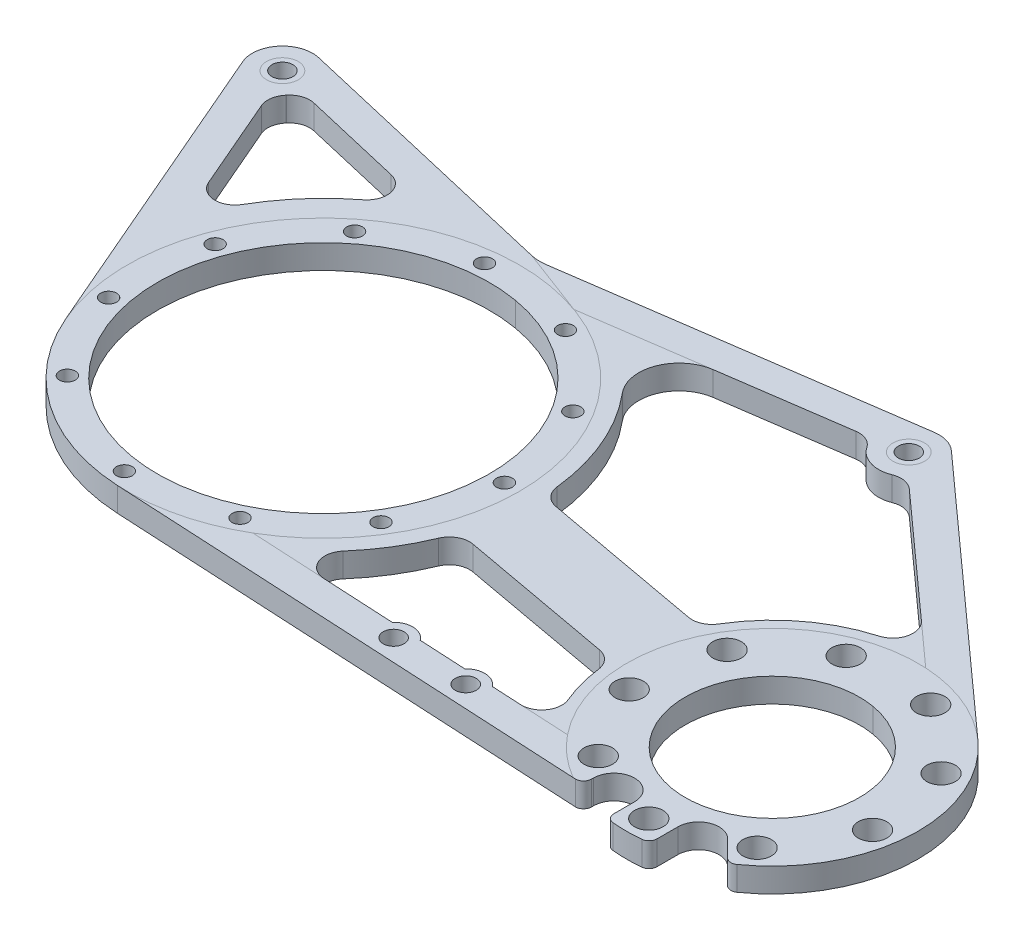
SolidWorks part; units mm, degrees
material "6061-T6 (SS)"
ref_plane "X-Y Datum" through (0, 0, 0) normal (0, 0, 1) x (1, 0, 0)
ref_plane "X-Z Datum" through (0, 0, 0) normal (0, 1, 0) x (1, 0, 0)
ref_plane "Y-Z Datum" through (0, 0, 0) normal (1, 0, 0) x (0, 0, -1)
sketch "Sketch2" plane through (0, 31.3819, 0) normal (0, 1, 0) x (1, 0, 0)
  line L0 (-693.7583, -176.702) -> (-693.7583, -183.2747) construction
  line L1 (-680.0808, -183.2747) -> (-680.0808, -176.702) construction
  line L2 (-668.9846, -172.1058) -> (-663.7197, -177.3707) construction
  line L3 (-693.7583, -176.702) -> (-693.7583, -183.2747)
  line L4 (-680.0808, -183.2747) -> (-680.0808, -176.702)
  line L5 (-668.9846, -172.1058) -> (-663.7197, -177.3707)
  line L6 (-966.641, -0.354) -> (-738.041, -0.354)
  line L7 (-727.7656, -5.5904) -> (-649.7224, -113.0358)
  line L9 (-977.8288, -19.0644) -> (-913.2312, -139.3061)
  line L10 (-706.7583, -177.279) -> (-706.7583, -176.702) construction
  line L11 (-706.7583, -177.279) -> (-706.7583, -176.702)
  line L12 (-861.9259, -171.8334) -> (-709.2983, -179.819)
  line L13 (-858.691, -110.0055) -> (-686.9195, -140.054) construction
  line L14 (-972.26, -24.9963) -> (-955.4664, -39.59) construction
  line L15 (-941.4162, -26.937) -> (-954.1775, -8.712) construction
  line L16 (-751.1929, -14.159) -> (-755.4346, -35.9995) construction
  line L17 (-737.4517, -41.8408) -> (-728.049, -21.6768) construction
  line L18 (-972.26, -24.9963) -> (-955.4664, -39.59)
  line L19 (-941.4162, -26.937) -> (-954.1775, -8.712)
  line L20 (-751.1929, -14.159) -> (-755.4346, -35.9995)
  line L21 (-737.4517, -41.8408) -> (-728.049, -21.6768)
  line L22 (-949.2186, -22.8753) -> (-746.0843, -28.2904)
  line L23 (-739.7146, -30.7335) -> (-656.1751, -105.8723)
  line L24 (-957.9647, -36.1729) -> (-915.5404, -134.527)
  arc A0 (-710.607, -179.4559) -> (-706.7583, -177.279) centre (-709.2983, -177.279) ccw construction
  arc A1 (-693.7583, -176.702) -> (-706.7583, -176.702) centre (-700.2583, -176.702) ccw construction
  arc A2 (-693.7583, -183.2747) -> (-691.4697, -185.8023) centre (-691.2183, -183.2747) ccw construction
  arc A3 (-691.4697, -185.8023) -> (-682.3694, -185.8023) centre (-686.9195, -140.054) ccw construction
  arc A4 (-682.3694, -185.8023) -> (-680.0808, -183.2747) centre (-682.6208, -183.2747) ccw construction
  arc A5 (-668.9846, -172.1058) -> (-680.0808, -176.702) centre (-673.5808, -176.702) ccw construction
  arc A6 (-663.7197, -177.3707) -> (-660.4619, -177.6519) centre (-661.9236, -175.5746) ccw construction
  arc A7 (-660.4619, -177.6519) -> (-710.607, -179.4559) centre (-686.9195, -140.054) ccw construction
  circle A8 centre (-858.691, -110.0055) radius 52.3875 construction
  circle A9 centre (-858.691, -110.0055) radius 61.9125 construction
  circle A10 centre (-738.041, -13.054) radius 12.7 construction
  circle A11 centre (-966.641, -13.054) radius 12.7 construction
  arc A12 (-710.607, -179.4559) -> (-706.7583, -177.279) centre (-709.2983, -177.279) ccw
  arc A13 (-693.7583, -176.702) -> (-706.7583, -176.702) centre (-700.2583, -176.702) ccw
  arc A14 (-693.7583, -183.2747) -> (-691.4697, -185.8023) centre (-691.2183, -183.2747) ccw
  arc A15 (-691.4697, -185.8023) -> (-682.3694, -185.8023) centre (-686.9195, -140.054) ccw
  arc A16 (-682.3694, -185.8023) -> (-680.0808, -183.2747) centre (-682.6208, -183.2747) ccw
  arc A17 (-668.9846, -172.1058) -> (-680.0808, -176.702) centre (-673.5808, -176.702) ccw
  arc A18 (-663.7197, -177.3707) -> (-660.4619, -177.6519) centre (-661.9236, -175.5746) ccw
  arc A19 (-660.4619, -177.6519) -> (-710.607, -179.4559) centre (-686.9195, -140.054) ccw
  circle A20 centre (-858.691, -110.0055) radius 52.3875
  circle A21 centre (-858.691, -110.0055) radius 61.9125
  circle A22 centre (-738.041, -13.054) radius 12.7
  circle A23 centre (-966.641, -13.054) radius 12.7
  circle A31 centre (-864.6648, -166.8424) radius 2.5 construction
  circle A39 centre (-864.6648, -166.8424) radius 2.5
  circle A40 centre (-686.9195, -140.054) radius 27.4955 construction
  circle A41 centre (-686.9195, -140.054) radius 27.4955
  circle A42 centre (-711.9883, -169.9297) radius 4.5 construction
  circle A43 centre (-725.3271, -146.8263) radius 4.5 construction
  circle A44 centre (-720.6945, -120.554) radius 4.5 construction
  circle A45 centre (-700.2583, -103.406) radius 4.5 construction
  circle A46 centre (-673.5808, -103.406) radius 4.5 construction
  circle A47 centre (-653.1446, -120.554) radius 4.5 construction
  circle A48 centre (-648.512, -146.8263) radius 4.5 construction
  circle A49 centre (-661.8508, -169.9297) radius 4.5 construction
  circle A50 centre (-686.9195, -179.054) radius 4.5 construction
  circle A51 centre (-711.9883, -169.9297) radius 4.5
  circle A52 centre (-725.3271, -146.8263) radius 4.5
  circle A53 centre (-720.6945, -120.554) radius 4.5
  circle A54 centre (-700.2583, -103.406) radius 4.5
  circle A55 centre (-673.5808, -103.406) radius 4.5
  circle A56 centre (-653.1446, -120.554) radius 4.5
  circle A57 centre (-648.512, -146.8263) radius 4.5
  circle A58 centre (-661.8508, -169.9297) radius 4.5
  circle A59 centre (-686.9195, -179.054) radius 4.5
  circle A60 centre (-966.641, -13.054) radius 3.3
  circle A61 centre (-738.041, -13.054) radius 3.3
  arc A62 (-955.4664, -39.59) -> (-941.4162, -26.937) centre (-949.2186, -32.4003) ccw construction
  arc A63 (-749.3237, -37.1863) -> (-742.8448, -38.4445) centre (-746.0843, -37.8154) ccw construction
  arc A64 (-742.8448, -38.4445) -> (-749.3237, -37.1863) centre (-746.0843, -37.8154) ccw construction
  arc A65 (-755.4346, -35.9995) -> (-737.4517, -41.8408) centre (-746.0843, -37.8154) ccw construction
  arc A66 (-955.4664, -39.59) -> (-941.4162, -26.937) centre (-949.2186, -32.4003) ccw
  arc A67 (-749.3237, -37.1863) -> (-742.8448, -38.4445) centre (-746.0843, -37.8154) ccw
  arc A68 (-742.8448, -38.4445) -> (-749.3237, -37.1863) centre (-746.0843, -37.8154) ccw
  arc A69 (-755.4346, -35.9995) -> (-737.4517, -41.8408) centre (-746.0843, -37.8154) ccw
  circle A70 centre (-949.2186, -32.4003) radius 3.3
  circle A71 centre (-949.2186, -32.4003) radius 9.525
  circle A72 centre (-746.0843, -37.8154) radius 9.525
  point P94 (-949.2186, -32.4003)
  dimension "D1" = 6.6
  dimension "D2" = 6.6
  dimension "D3" = 6.6
extrude "Boss-Extrude1" add sketch "Sketch2" along normal blind 7.62 contours A21 A39 A20 | A18 A19 A12 L11 A13 L3 A14 A15 A16 L4 A17 L5 A59 A58 A57 A56 A55 A54 A53 A52 A51 A41 | L13 A21 L12 A12 A19 | A21 L13 A19 L23 L21 A69 L20 L22 L19 A66 L18 L24 | A69 A72 A68 A67 | A72 L22 L20 | A72 L21 L23 | A71 L24 L18 | A71 L19 L22 | A71 A66 L22 A70 region at (-700.2583, 31.3819, 168.9016) region at (-773.051, 31.3819, 154.3682) region at (-890.9045, 31.3819, 160.8157) region at (-806.8861, 31.3819, 67.2042) region at (-956.9478, 31.3819, 38.0512) region at (-736.2382, 31.3819, 35.8095) region at (-956.6903, 31.3819, 37.8629) region at (-748.9437, 31.3819, 46.6182) region at (-752.4763, 31.3819, 29.8585) region at (-944.5842, 31.3819, 23.8004)
sketch "Sketch3" plane through (0, 31.3819, 0) normal (0, -1, 0) x (1, 0, 0)
  line L1 (-949.2186, 22.8753) -> (-746.0843, 28.2904) construction
  line L5 (-861.9259, 171.8334) -> (-709.2983, 179.819) construction
  line L6 (-977.8288, 19.0644) -> (-913.2312, 139.3061) construction
  line L7 (-727.7656, 5.5904) -> (-649.7224, 113.0358) construction
  line L13 (-751.1929, 14.159) -> (-755.4346, 35.9995) construction
  line L16 (-966.641, 0.354) -> (-738.041, 0.354) construction
  line L19 (-663.7197, 177.3707) -> (-668.9846, 172.1058)
  line L20 (-680.0808, 176.702) -> (-680.0808, 183.2747)
  line L21 (-693.7583, 183.2747) -> (-693.7583, 176.702)
  line L22 (-706.7583, 176.702) -> (-706.7583, 177.279)
  line L23 (-663.7197, 177.3707) -> (-668.9846, 172.1058)
  line L24 (-680.0808, 176.702) -> (-680.0808, 183.2747)
  line L25 (-693.7583, 183.2747) -> (-693.7583, 176.702)
  line L26 (-706.7583, 176.702) -> (-706.7583, 177.279)
  line L28 (-861.9259, 171.8334) -> (-709.2983, 179.819)
  line L29 (-977.8288, 19.0644) -> (-913.2312, 139.3061)
  line L30 (-727.7656, 5.5904) -> (-649.7224, 113.0358)
  line L31 (-966.641, 0.354) -> (-738.041, 0.354)
  line L34 (-737.4517, 41.8408) -> (-728.049, 21.6768) construction
  line L35 (-972.26, 24.9963) -> (-955.4664, 39.59) construction
  line L36 (-947.0539, 23.1246) -> (-856.9722, 44.1471)
  line L37 (-856.9722, 44.1471) -> (-747.4408, 28.3875)
  line L44 (-941.4162, 26.937) -> (-954.1775, 8.712) construction
  line L45 (-957.9647, 36.1729) -> (-915.5404, 134.527) construction
  line L46 (-739.7146, 30.7335) -> (-656.1751, 105.8723) construction
  line L47 (-861.9259, 171.8334) -> (-709.2983, 179.819)
  line L48 (-977.8288, 19.0644) -> (-913.2312, 139.3061)
  line L49 (-727.7656, 5.5904) -> (-649.7224, 113.0358)
  line L50 (-966.641, 0.354) -> (-738.041, 0.354)
  line L51 (-949.2186, 22.8753) -> (-746.0843, 28.2904)
  line L52 (-751.1929, 14.159) -> (-755.4346, 35.9995)
  line L53 (-737.4517, 41.8408) -> (-728.049, 21.6768)
  line L54 (-972.26, 24.9963) -> (-955.4664, 39.59)
  line L55 (-941.4162, 26.937) -> (-954.1775, 8.712)
  line L56 (-957.9647, 36.1729) -> (-915.5404, 134.527)
  line L57 (-739.7146, 30.7335) -> (-656.1751, 105.8723)
  arc A1 (-737.4517, 41.8408) -> (-755.4346, 35.9995) centre (-746.0843, 37.8154) ccw construction
  circle A3 centre (-966.641, 13.054) radius 12.7
  circle A5 centre (-966.641, 13.054) radius 12.7
  circle A7 centre (-738.041, 13.054) radius 12.7
  circle A9 centre (-738.041, 13.054) radius 12.7
  circle A11 centre (-858.691, 110.0055) radius 61.9125
  circle A13 centre (-858.691, 110.0055) radius 61.9125
  circle A15 centre (-858.691, 110.0055) radius 52.3875
  circle A17 centre (-858.691, 110.0055) radius 52.3875
  circle A19 centre (-686.9195, 140.054) radius 27.4955
  circle A21 centre (-686.9195, 140.054) radius 27.4955
  circle A23 centre (-864.6648, 166.8424) radius 2.5
  circle A25 centre (-864.6648, 166.8424) radius 2.5
  circle A51 centre (-720.6945, 120.554) radius 4.5
  circle A52 centre (-720.6945, 120.554) radius 4.5
  circle A68 centre (-725.3271, 146.8263) radius 4.5
  circle A69 centre (-725.3271, 146.8263) radius 4.5
  circle A70 centre (-711.9883, 169.9297) radius 4.5
  circle A71 centre (-711.9883, 169.9297) radius 4.5
  circle A72 centre (-738.041, 13.054) radius 3.3
  circle A73 centre (-738.041, 13.054) radius 3.3
  circle A74 centre (-966.641, 13.054) radius 3.3
  circle A75 centre (-966.641, 13.054) radius 3.3
  circle A76 centre (-686.9195, 179.054) radius 4.5
  circle A77 centre (-686.9195, 179.054) radius 4.5
  circle A78 centre (-661.8508, 169.9297) radius 4.5
  circle A79 centre (-661.8508, 169.9297) radius 4.5
  circle A80 centre (-648.512, 146.8263) radius 4.5
  circle A81 centre (-648.512, 146.8263) radius 4.5
  circle A82 centre (-653.1446, 120.554) radius 4.5
  circle A83 centre (-653.1446, 120.554) radius 4.5
  circle A84 centre (-673.5808, 103.406) radius 4.5
  circle A85 centre (-673.5808, 103.406) radius 4.5
  circle A86 centre (-700.2583, 103.406) radius 4.5
  circle A87 centre (-700.2583, 103.406) radius 4.5
  arc A95 (-710.607, 179.4559) -> (-660.4619, 177.6519) centre (-686.9195, 140.054) ccw
  arc A96 (-660.4619, 177.6519) -> (-663.7197, 177.3707) centre (-661.9236, 175.5746) ccw
  arc A97 (-680.0808, 176.702) -> (-668.9846, 172.1058) centre (-673.5808, 176.702) ccw
  arc A98 (-680.0808, 183.2747) -> (-682.3694, 185.8023) centre (-682.6208, 183.2747) ccw
  arc A99 (-682.3694, 185.8023) -> (-691.4697, 185.8023) centre (-686.9195, 140.054) ccw
  arc A100 (-691.4697, 185.8023) -> (-693.7583, 183.2747) centre (-691.2183, 183.2747) ccw
  arc A101 (-706.7583, 176.702) -> (-693.7583, 176.702) centre (-700.2583, 176.702) ccw
  arc A102 (-706.7583, 177.279) -> (-710.607, 179.4559) centre (-709.2983, 177.279) ccw
  arc A103 (-710.607, 179.4559) -> (-660.4619, 177.6519) centre (-686.9195, 140.054) ccw
  arc A104 (-660.4619, 177.6519) -> (-663.7197, 177.3707) centre (-661.9236, 175.5746) ccw
  arc A105 (-680.0808, 176.702) -> (-668.9846, 172.1058) centre (-673.5808, 176.702) ccw
  arc A106 (-680.0808, 183.2747) -> (-682.3694, 185.8023) centre (-682.6208, 183.2747) ccw
  arc A107 (-682.3694, 185.8023) -> (-691.4697, 185.8023) centre (-686.9195, 140.054) ccw
  arc A108 (-691.4697, 185.8023) -> (-693.7583, 183.2747) centre (-691.2183, 183.2747) ccw
  arc A109 (-706.7583, 176.702) -> (-693.7583, 176.702) centre (-700.2583, 176.702) ccw
  arc A110 (-706.7583, 177.279) -> (-710.607, 179.4559) centre (-709.2983, 177.279) ccw
  circle A152 centre (-746.0843, 37.8154) radius 9.525
  circle A153 centre (-746.0843, 37.8154) radius 9.525
  circle A154 centre (-949.2186, 32.4003) radius 9.525
  circle A155 centre (-949.2186, 32.4003) radius 9.525
  circle A156 centre (-949.2186, 32.4003) radius 3.3
  circle A157 centre (-949.2186, 32.4003) radius 3.3
  arc A158 (-941.4162, 26.937) -> (-955.4664, 39.59) centre (-949.2186, 32.4003) ccw construction
  arc A159 (-742.8448, 38.4445) -> (-749.3237, 37.1863) centre (-746.0843, 37.8154) ccw
  arc A160 (-749.3237, 37.1863) -> (-742.8448, 38.4445) centre (-746.0843, 37.8154) ccw
  arc A161 (-742.8448, 38.4445) -> (-749.3237, 37.1863) centre (-746.0843, 37.8154) ccw
  arc A162 (-749.3237, 37.1863) -> (-742.8448, 38.4445) centre (-746.0843, 37.8154) ccw
  arc A163 (-737.4517, 41.8408) -> (-755.4346, 35.9995) centre (-746.0843, 37.8154) ccw
  arc A164 (-941.4162, 26.937) -> (-955.4664, 39.59) centre (-949.2186, 32.4003) ccw
  dimension "D24" = 0
  dimension "D25" = 0
  dimension "D26" = 90.0818
  dimension "D27" = 21.0225
  dimension "D1" = 0
  dimension "D2" = 0
  dimension "D3" = 0
  dimension "D4" = 0
  dimension "D5" = 0
  dimension "D6" = 0
  dimension "D14" = 0
  dimension "D15" = 0
  dimension "D16" = 0
  dimension "D17" = 0
  dimension "D18" = 0
  dimension "D19" = 0
  dimension "D20" = 0
  dimension "D21" = 0
  dimension "D22" = 0
  dimension "D23" = 0
  dimension "D52" = 0
  dimension "D53" = 0
  dimension "D54" = 0
  dimension "D55" = 0
ref_point "Point1"
ref_point "Point2"
ref_plane "Plane1" through (-858.691, 31.3819, 110.0055) normal (0.985, 0, 0.1723) x (0.1723, 0, -0.985)
ref_plane "Plane2" through (-686.9195, 31.3819, 140.054) normal (-0.985, 0, -0.1723) x (-0.1723, 0, 0.985)
split line "Split Line1"
split line "Split Line2"
ref_axis "Axis1" through (-858.691, 39.0019, 110.0055) along (0, -1, 0)
ref_axis "Axis2" through (-686.9195, 39.0019, 140.054) along (0, -1, 0)
extrude "Cut-Extrude1" cut sketch "Sketch3" against normal through all contours L36 L55 L51 L52 L37 | A155 L51 L55 L36 | A153 L37 L52 L51 region at (-751.5495, 31.3819, 28.5688) region at (-850.6911, 31.3819, 31.7926) region at (-945.2616, 31.3819, 23.2848)
fillet "Fillet2" radius 12.7 1 edges at (-856.9722, 35.1919, 44.1471)
sketch "Sketch4" plane through (0, 31.3819, 0) normal (0, -1, 0) x (1, 0, 0)
  line L0 (-861.9259, 171.8334) -> (-709.2983, 179.819) construction
  line L1 (-727.7656, 5.5904) -> (-649.7224, 113.0358) construction
  line L2 (-977.8288, 19.0644) -> (-913.2312, 139.3061) construction
  line L4 (-706.7583, 176.702) -> (-706.7583, 177.279)
  line L5 (-663.7197, 177.3707) -> (-668.9846, 172.1058)
  line L6 (-680.0808, 176.702) -> (-680.0808, 183.2747)
  line L7 (-693.7583, 183.2747) -> (-693.7583, 176.702)
  line L8 (-706.7583, 176.702) -> (-706.7583, 177.279)
  line L9 (-663.7197, 177.3707) -> (-668.9846, 172.1058)
  line L10 (-680.0808, 176.702) -> (-680.0808, 183.2747)
  line L11 (-693.7583, 183.2747) -> (-693.7583, 176.702)
  line L13 (-966.641, 0.354) -> (-738.041, 0.354) construction
  line L14 (-861.9259, 171.8334) -> (-709.2983, 179.819)
  line L15 (-727.7656, 5.5904) -> (-649.7224, 113.0358)
  line L16 (-977.8288, 19.0644) -> (-913.2312, 139.3061)
  line L17 (-861.9259, 171.8334) -> (-709.2983, 179.819) construction
  line L19 (-966.641, 0.354) -> (-738.041, 0.354)
  line L20 (-924.6037, 87.863) -> (-948.1369, 33.3048)
  line L21 (-948.1369, 33.3048) -> (-888.5504, 47.2106)
  line L22 (-732.3805, 168.4374) -> (-812.7818, 164.2308) construction
  line L23 (-812.7818, 164.2308) -> (-733.9678, 114.3873) construction
  line L24 (-799.833, 147.0258) -> (-703.8013, 86.2934) construction
  line L25 (-703.8013, 86.2934) -> (-794.9695, 82.1785) construction
  line L26 (-824.108, 49.6832) -> (-755.4008, 39.7974) construction
  line L27 (-798.9847, 74.3695) -> (-701.5009, 78.7695) construction
  line L28 (-701.5009, 78.7695) -> (-739.4428, 44.643) construction
  line L29 (-977.8288, 19.0644) -> (-913.2312, 139.3061) construction
  line L30 (-727.7656, 5.5904) -> (-649.7224, 113.0358) construction
  line L31 (-966.641, 0.354) -> (-738.041, 0.354) construction
  line L32 (-663.7197, 177.3707) -> (-668.9846, 172.1058)
  line L33 (-680.0808, 176.702) -> (-680.0808, 183.2747)
  line L34 (-693.7583, 183.2747) -> (-693.7583, 176.702)
  line L35 (-706.7583, 176.702) -> (-706.7583, 177.279)
  line L36 (-663.7197, 177.3707) -> (-668.9846, 172.1058)
  line L37 (-680.0808, 176.702) -> (-680.0808, 183.2747)
  line L38 (-693.7583, 183.2747) -> (-693.7583, 176.702)
  line L39 (-706.7583, 176.702) -> (-706.7583, 177.279)
  line L40 (-949.2186, 22.8753) -> (-746.0843, 28.2904) construction
  line L41 (-751.1929, 14.159) -> (-755.4346, 35.9995) construction
  line L42 (-737.4517, 41.8408) -> (-728.049, 21.6768) construction
  line L43 (-972.26, 24.9963) -> (-955.4664, 39.59) construction
  line L44 (-941.4162, 26.937) -> (-954.1775, 8.712) construction
  line L45 (-957.9647, 36.1729) -> (-915.5404, 134.527) construction
  line L46 (-739.7146, 30.7335) -> (-656.1751, 105.8723) construction
  line L47 (-861.9259, 171.8334) -> (-709.2983, 179.819)
  line L48 (-977.8288, 19.0644) -> (-913.2312, 139.3061)
  line L49 (-727.7656, 5.5904) -> (-649.7224, 113.0358)
  line L50 (-966.641, 0.354) -> (-738.041, 0.354)
  line L51 (-949.2186, 22.8753) -> (-746.0843, 28.2904)
  line L52 (-751.1929, 14.159) -> (-755.4346, 35.9995)
  line L53 (-737.4517, 41.8408) -> (-728.049, 21.6768)
  line L54 (-972.26, 24.9963) -> (-955.4664, 39.59)
  line L55 (-941.4162, 26.937) -> (-954.1775, 8.712)
  line L56 (-957.9647, 36.1729) -> (-915.5404, 134.527)
  line L57 (-739.7146, 30.7335) -> (-656.1751, 105.8723)
  line L58 (-947.0539, 23.1246) -> (-859.3005, 43.6037) construction
  line L60 (-854.6056, 43.8066) -> (-747.4408, 28.3875) construction
  circle A1 centre (-858.691, 110.0055) radius 52.3875
  circle A2 centre (-858.691, 110.0055) radius 52.3875
  circle A3 centre (-858.691, 110.0055) radius 61.9125
  circle A4 centre (-858.691, 110.0055) radius 61.9125
  circle A5 centre (-738.041, 13.054) radius 12.7
  circle A6 centre (-738.041, 13.054) radius 12.7
  circle A7 centre (-966.641, 13.054) radius 12.7
  circle A8 centre (-966.641, 13.054) radius 12.7
  circle A17 centre (-864.6648, 166.8424) radius 2.5
  circle A18 centre (-864.6648, 166.8424) radius 2.5
  circle A19 centre (-686.9195, 140.054) radius 27.4955
  circle A20 centre (-686.9195, 140.054) radius 27.4955
  circle A21 centre (-725.3271, 146.8263) radius 4.5
  circle A22 centre (-725.3271, 146.8263) radius 4.5
  circle A23 centre (-720.6945, 120.554) radius 4.5
  circle A24 centre (-720.6945, 120.554) radius 4.5
  circle A31 centre (-661.8508, 169.9297) radius 4.5
  circle A32 centre (-661.8508, 169.9297) radius 4.5
  circle A33 centre (-686.9195, 179.054) radius 4.5
  circle A34 centre (-686.9195, 179.054) radius 4.5
  circle A35 centre (-966.641, 13.054) radius 3.3
  circle A36 centre (-966.641, 13.054) radius 3.3
  circle A37 centre (-738.041, 13.054) radius 3.3
  circle A38 centre (-738.041, 13.054) radius 3.3
  circle A39 centre (-711.9883, 169.9297) radius 4.5
  circle A40 centre (-711.9883, 169.9297) radius 4.5
  circle A41 centre (-700.2583, 103.406) radius 4.5
  circle A42 centre (-700.2583, 103.406) radius 4.5
  circle A43 centre (-673.5808, 103.406) radius 4.5
  circle A44 centre (-673.5808, 103.406) radius 4.5
  circle A45 centre (-653.1446, 120.554) radius 4.5
  circle A46 centre (-653.1446, 120.554) radius 4.5
  circle A47 centre (-648.512, 146.8263) radius 4.5
  circle A48 centre (-648.512, 146.8263) radius 4.5
  arc A49 (-888.5504, 47.2106) -> (-924.6037, 87.863) centre (-858.691, 110.0055) cw
  arc A50 (-732.3805, 168.4374) -> (-733.9678, 114.3873) centre (-686.9195, 140.054) ccw construction
  arc A51 (-799.833, 147.0258) -> (-794.9695, 82.1785) centre (-858.691, 110.0055) cw construction
  arc A52 (-824.108, 49.6832) -> (-798.9847, 74.3695) centre (-858.691, 110.0055) ccw construction
  arc A53 (-737.4517, 41.8408) -> (-755.4346, 35.9995) centre (-746.0843, 37.8154) ccw construction
  circle A54 centre (-966.641, 13.054) radius 12.7
  circle A55 centre (-966.641, 13.054) radius 12.7
  arc A56 (-706.7583, 177.279) -> (-710.607, 179.4559) centre (-709.2983, 177.279) ccw
  arc A57 (-710.607, 179.4559) -> (-660.4619, 177.6519) centre (-686.9195, 140.054) ccw
  arc A58 (-660.4619, 177.6519) -> (-663.7197, 177.3707) centre (-661.9236, 175.5746) ccw
  arc A59 (-680.0808, 176.702) -> (-668.9846, 172.1058) centre (-673.5808, 176.702) ccw
  arc A60 (-680.0808, 183.2747) -> (-682.3694, 185.8023) centre (-682.6208, 183.2747) ccw
  arc A61 (-682.3694, 185.8023) -> (-691.4697, 185.8023) centre (-686.9195, 140.054) ccw
  arc A62 (-691.4697, 185.8023) -> (-693.7583, 183.2747) centre (-691.2183, 183.2747) ccw
  arc A63 (-706.7583, 176.702) -> (-693.7583, 176.702) centre (-700.2583, 176.702) ccw
  arc A64 (-706.7583, 177.279) -> (-710.607, 179.4559) centre (-709.2983, 177.279) ccw
  arc A65 (-710.607, 179.4559) -> (-660.4619, 177.6519) centre (-686.9195, 140.054) ccw
  arc A66 (-660.4619, 177.6519) -> (-663.7197, 177.3707) centre (-661.9236, 175.5746) ccw
  arc A67 (-680.0808, 176.702) -> (-668.9846, 172.1058) centre (-673.5808, 176.702) ccw
  arc A68 (-680.0808, 183.2747) -> (-682.3694, 185.8023) centre (-682.6208, 183.2747) ccw
  arc A69 (-682.3694, 185.8023) -> (-691.4697, 185.8023) centre (-686.9195, 140.054) ccw
  arc A70 (-691.4697, 185.8023) -> (-693.7583, 183.2747) centre (-691.2183, 183.2747) ccw
  arc A71 (-706.7583, 176.702) -> (-693.7583, 176.702) centre (-700.2583, 176.702) ccw
  circle A72 centre (-738.041, 13.054) radius 12.7
  circle A73 centre (-738.041, 13.054) radius 12.7
  circle A74 centre (-858.691, 110.0055) radius 61.9125
  circle A75 centre (-858.691, 110.0055) radius 61.9125
  circle A76 centre (-858.691, 110.0055) radius 52.3875
  circle A77 centre (-858.691, 110.0055) radius 52.3875
  circle A78 centre (-686.9195, 140.054) radius 27.4955
  circle A79 centre (-686.9195, 140.054) radius 27.4955
  circle A80 centre (-864.6648, 166.8424) radius 2.5
  circle A81 centre (-864.6648, 166.8424) radius 2.5
  circle A96 centre (-720.6945, 120.554) radius 4.5
  circle A97 centre (-720.6945, 120.554) radius 4.5
  circle A98 centre (-725.3271, 146.8263) radius 4.5
  circle A99 centre (-725.3271, 146.8263) radius 4.5
  circle A100 centre (-711.9883, 169.9297) radius 4.5
  circle A101 centre (-711.9883, 169.9297) radius 4.5
  circle A102 centre (-738.041, 13.054) radius 3.3
  circle A103 centre (-738.041, 13.054) radius 3.3
  circle A104 centre (-966.641, 13.054) radius 3.3
  circle A105 centre (-966.641, 13.054) radius 3.3
  circle A106 centre (-686.9195, 179.054) radius 4.5
  circle A107 centre (-686.9195, 179.054) radius 4.5
  circle A108 centre (-661.8508, 169.9297) radius 4.5
  circle A109 centre (-661.8508, 169.9297) radius 4.5
  circle A110 centre (-648.512, 146.8263) radius 4.5
  circle A111 centre (-648.512, 146.8263) radius 4.5
  circle A112 centre (-653.1446, 120.554) radius 4.5
  circle A113 centre (-653.1446, 120.554) radius 4.5
  circle A114 centre (-673.5808, 103.406) radius 4.5
  circle A115 centre (-673.5808, 103.406) radius 4.5
  circle A116 centre (-700.2583, 103.406) radius 4.5
  circle A117 centre (-700.2583, 103.406) radius 4.5
  circle A118 centre (-746.0843, 37.8154) radius 9.525
  circle A119 centre (-746.0843, 37.8154) radius 9.525
  circle A120 centre (-949.2186, 32.4003) radius 9.525
  circle A121 centre (-949.2186, 32.4003) radius 9.525
  circle A122 centre (-949.2186, 32.4003) radius 3.3
  circle A123 centre (-949.2186, 32.4003) radius 3.3
  arc A124 (-941.4162, 26.937) -> (-955.4664, 39.59) centre (-949.2186, 32.4003) ccw construction
  arc A125 (-742.8448, 38.4445) -> (-749.3237, 37.1863) centre (-746.0843, 37.8154) ccw
  arc A126 (-749.3237, 37.1863) -> (-742.8448, 38.4445) centre (-746.0843, 37.8154) ccw
  arc A127 (-742.8448, 38.4445) -> (-749.3237, 37.1863) centre (-746.0843, 37.8154) ccw
  arc A128 (-749.3237, 37.1863) -> (-742.8448, 38.4445) centre (-746.0843, 37.8154) ccw
  arc A129 (-737.4517, 41.8408) -> (-755.4346, 35.9995) centre (-746.0843, 37.8154) ccw
  arc A130 (-941.4162, 26.937) -> (-955.4664, 39.59) centre (-949.2186, 32.4003) ccw
  arc A135 (-710.607, 179.4559) -> (-660.4619, 177.6519) centre (-686.9195, 140.054) ccw
  arc A136 (-660.4619, 177.6519) -> (-663.7197, 177.3707) centre (-661.9236, 175.5746) ccw
  arc A137 (-680.0808, 176.702) -> (-668.9846, 172.1058) centre (-673.5808, 176.702) ccw
  arc A138 (-680.0808, 183.2747) -> (-682.3694, 185.8023) centre (-682.6208, 183.2747) ccw
  arc A139 (-682.3694, 185.8023) -> (-691.4697, 185.8023) centre (-686.9195, 140.054) ccw
  arc A140 (-691.4697, 185.8023) -> (-693.7583, 183.2747) centre (-691.2183, 183.2747) ccw
  arc A141 (-706.7583, 176.702) -> (-693.7583, 176.702) centre (-700.2583, 176.702) ccw
  arc A142 (-706.7583, 177.279) -> (-710.607, 179.4559) centre (-709.2983, 177.279) ccw
  arc A143 (-710.607, 179.4559) -> (-660.4619, 177.6519) centre (-686.9195, 140.054) ccw
  arc A144 (-660.4619, 177.6519) -> (-663.7197, 177.3707) centre (-661.9236, 175.5746) ccw
  arc A145 (-680.0808, 176.702) -> (-668.9846, 172.1058) centre (-673.5808, 176.702) ccw
  arc A146 (-680.0808, 183.2747) -> (-682.3694, 185.8023) centre (-682.6208, 183.2747) ccw
  arc A147 (-682.3694, 185.8023) -> (-691.4697, 185.8023) centre (-686.9195, 140.054) ccw
  arc A148 (-691.4697, 185.8023) -> (-693.7583, 183.2747) centre (-691.2183, 183.2747) ccw
  arc A149 (-706.7583, 176.702) -> (-693.7583, 176.702) centre (-700.2583, 176.702) ccw
  arc A150 (-706.7583, 177.279) -> (-710.607, 179.4559) centre (-709.2983, 177.279) ccw
  dimension "D26" = 7.62
  dimension "D29" = 7.62
  dimension "D30" = 7.62
  dimension "D35" = 0
  dimension "D39" = 7.62
  dimension "D27" = 0
  dimension "D28" = 0
  dimension "D31" = 10.16
  dimension "D32" = 7.62
  dimension "D33" = 93.2524
  dimension "D34" = 49.8435
  dimension "D36" = 91.1683
  dimension "D37" = 4.1149
  dimension "D38" = 10.16
  dimension "D40" = 7.62
  dimension "D67" = 10.16
  dimension "D68" = 10.16
  dimension "D69" = 10.16
  dimension "D1" = 0
  dimension "D2" = 0
  dimension "D3" = 0
  dimension "D4" = 0
  dimension "D9" = 0
  dimension "D10" = 0
  dimension "D11" = 0
  dimension "D12" = 0
  dimension "D16" = 0
  dimension "D17" = 0
  dimension "D18" = 0
  dimension "D19" = 0
  dimension "D20" = 0
  dimension "D21" = 0
  dimension "D22" = 0
  dimension "D23" = 0
  dimension "D24" = 0
  dimension "D25" = 0
  dimension "D41" = 0
  dimension "D42" = 0
  dimension "D43" = 0
  dimension "D51" = 0
  dimension "D52" = 0
  dimension "D53" = 0
  dimension "D54" = 0
  dimension "D55" = 0
  dimension "D56" = 0
  dimension "D57" = 0
  dimension "D58" = 0
  dimension "D59" = 0
  dimension "D60" = 0
  dimension "D61" = 0
  dimension "D62" = 0
  dimension "D63" = 0
  dimension "D64" = 0
  dimension "D65" = 0
  dimension "D66" = 0
extrude "Cut-Extrude2" cut sketch "Sketch4" against normal through all contours L21 A49 L20 A8 | A52 L26 A6 L28 L27 | L24 A51 L25 | A50 L22 L23 region at (-829.4195, 31.3819, 24.9298) region at (-921.8341, 31.3819, 54.9859)
fillet "Fillet3" [suppressed] radius 6.604
split line "Split Line3"
sketch "Sketch2<4>" plane through (0, 31.3819, 0) normal (0, 1, 0) x (1, 0, 0) same geometry as "Sketch2"
pattern_circular "CirPattern2" count 11 every 32 about axis through (-858.691, 39.0019, 110.0055) along (0, -1, 0) reverse direction yes of face at (-867.1648, 39.0019, 166.8424)
sketch "Sketch5" plane through (0, 39.0019, 0) normal (0, 1, 0) x (1, 0, 0)
  circle A0 centre (-949.2186, -32.4003) radius 5
  circle A1 centre (-746.0843, -37.8154) radius 5
  dimension "D1" = 10
split line "Split Line4"
sketch "Sketch6" [suppressed] plane through (0, 31.3819, 0) normal (0, -1, 0) x (1, 0, 0)
  line L0 (-743.6056, 167.8501) -> (-792.0577, 165.3151) construction
  line L1 (-724.7926, 85.346) -> (-785.1492, 82.6217) construction
  line L2 (-724.7926, 85.346) -> (-785.1492, 82.6217)
  line L3 (-791.5915, 128.2378) -> (-796.8267, 141.9391)
  line L4 (-743.6056, 167.8501) -> (-781.2512, 165.8805)
  line L5 (-781.2512, 165.8805) -> (-792.0577, 165.3151)
  arc A0 (-791.8001, 91.022) -> (-791.5915, 128.2378) centre (-858.691, 110.0055) ccw construction
  arc A1 (-791.8001, 91.022) -> (-791.5915, 128.2378) centre (-858.691, 110.0055) ccw
  circle A2 centre (-780.3284, 148.243) radius 17.6616 construction
  circle A3 centre (-744.0706, 102.1866) radius 14.9639 construction
  arc A4 (-737.0797, 158.9293) -> (-739.7578, 131.0856) centre (-686.9195, 140.054) ccw construction
  arc A5 (-724.7926, 85.346) -> (-721.5605, 97.5247) centre (-725.0904, 91.9433) ccw construction
  arc A6 (-737.0797, 158.9293) -> (-743.6056, 167.8501) centre (-743.2606, 161.2551) ccw construction
  arc A7 (-737.0797, 158.9293) -> (-739.7578, 131.0856) centre (-686.9195, 140.054) ccw
  arc A8 (-737.0797, 158.9293) -> (-743.6056, 167.8501) centre (-743.2606, 161.2551) ccw
  arc A9 (-724.7926, 85.346) -> (-721.5605, 97.5247) centre (-725.0904, 91.9433) ccw
  arc A10 (-791.8001, 91.022) -> (-785.1492, 82.6217) centre (-785.447, 89.219) ccw construction
  arc A11 (-791.8001, 91.022) -> (-785.1492, 82.6217) centre (-785.447, 89.219) ccw
  arc A13 (-739.7578, 131.0856) -> (-731.5964, 110.4517) centre (-686.9195, 140.054) ccw
  arc A14 (-721.5605, 97.5247) -> (-731.5964, 110.4517) centre (-640.5401, 170.7843) cw
  arc A15 (-792.0577, 165.3151) -> (-798.1017, 160.3912) centre (-791.7127, 158.7201) ccw
  arc A17 (-792.0577, 165.3151) -> (-795.2425, 153.1386) centre (-791.7127, 158.7201) ccw construction
  arc A18 (-798.1017, 160.3912) -> (-796.8267, 141.9391) centre (-767.2093, 153.2558) ccw
  dimension "D3" = 31.7058
  dimension "D1" = 11.2631
  dimension "D2" = 22.5101
extrude "Cut-Extrude3" [suppressed] cut sketch "Sketch6" against normal through all
sketch "Sketch7" plane through (0, 31.3819, 0) normal (0, -1, 0) x (1, 0, 0)
  line L0 (-859.3005, 43.6037) -> (-836.8375, 52.0781)
  arc A0 (-915.5404, 134.527) -> (-861.9259, 171.8334) centre (-858.691, 110.0055) ccw construction
split line "Split Line5"
sketch "Sketch8" plane through (0, 39.0019, 0) normal (0, 1, 0) x (1, 0, 0)
  line L0 (-859.3005, -43.6037) -> (-836.8375, -52.0781) construction
  line L1 (-859.3005, -43.6037) -> (-836.8375, -52.0781)
  line L2 (-732.3805, -168.4374) -> (-812.7818, -164.2308) construction
  line L3 (-824.108, -49.6832) -> (-755.4008, -39.7974) construction
  line L4 (-701.5009, -78.7695) -> (-739.4428, -44.643) construction
  line L5 (-732.3805, -168.4374) -> (-812.7818, -164.2308)
  line L6 (-824.108, -49.6832) -> (-755.4008, -39.7974)
  line L7 (-709.5634, -179.8051) -> (-709.2983, -179.819)
  line L8 (-668.9846, -172.1058) -> (-663.7197, -177.3707)
  line L9 (-680.0808, -183.2747) -> (-680.0808, -176.702)
  line L10 (-693.7583, -176.702) -> (-693.7583, -183.2747)
  line L11 (-706.7583, -177.279) -> (-706.7583, -176.702)
  line L12 (-709.5634, -179.8051) -> (-709.2983, -179.819)
  line L13 (-668.9846, -172.1058) -> (-663.7197, -177.3707)
  line L14 (-680.0808, -183.2747) -> (-680.0808, -176.702)
  line L15 (-693.7583, -176.702) -> (-693.7583, -183.2747)
  line L16 (-706.7583, -177.279) -> (-706.7583, -176.702)
  line L17 (-701.5009, -78.7695) -> (-739.4428, -44.643)
  line L18 (-701.5009, -78.7695) -> (-684.402, -94.149)
  line L19 (-824.108, -49.6832) -> (-837.9186, -51.6702)
  line L20 (-732.3805, -168.4374) -> (-722.6816, -168.9449)
  line L21 (-812.7818, -164.2308) -> (-827.4586, -163.4628)
  circle A0 centre (-746.0843, -37.8154) radius 9.525 construction
  circle A1 centre (-746.0843, -37.8154) radius 9.525 construction
  arc A2 (-739.4428, -44.643) -> (-755.4008, -39.7974) centre (-746.0843, -37.8154) cw
  arc A3 (-915.5404, -134.527) -> (-861.9259, -171.8334) centre (-858.691, -110.0055) ccw
  arc A4 (-836.8375, -52.0781) -> (-915.5404, -134.527) centre (-858.691, -110.0055) ccw
  arc A5 (-861.9259, -171.8334) -> (-836.8375, -52.0781) centre (-858.691, -110.0055) ccw
  arc A6 (-915.5404, -134.527) -> (-861.9259, -171.8334) centre (-858.691, -110.0055) ccw
  arc A7 (-836.8375, -52.0781) -> (-915.5404, -134.527) centre (-858.691, -110.0055) ccw
  arc A8 (-861.9259, -171.8334) -> (-836.8375, -52.0781) centre (-858.691, -110.0055) ccw
  arc A16 (-710.607, -179.4559) -> (-709.5634, -179.8051) centre (-709.2983, -177.279) ccw
  arc A17 (-656.1751, -105.8723) -> (-710.607, -179.4559) centre (-686.9195, -140.054) ccw
  arc A18 (-660.4619, -177.6519) -> (-656.1751, -105.8723) centre (-686.9195, -140.054) ccw
  arc A19 (-663.7197, -177.3707) -> (-660.4619, -177.6519) centre (-661.9236, -175.5746) ccw
  arc A20 (-668.9846, -172.1058) -> (-680.0808, -176.702) centre (-673.5808, -176.702) ccw
  arc A21 (-682.3694, -185.8023) -> (-680.0808, -183.2747) centre (-682.6208, -183.2747) ccw
  arc A22 (-691.4697, -185.8023) -> (-682.3694, -185.8023) centre (-686.9195, -140.054) ccw
  arc A23 (-693.7583, -183.2747) -> (-691.4697, -185.8023) centre (-691.2183, -183.2747) ccw
  arc A24 (-693.7583, -176.702) -> (-706.7583, -176.702) centre (-700.2583, -176.702) ccw
  arc A25 (-709.2983, -179.819) -> (-706.7583, -177.279) centre (-709.2983, -177.279) ccw
  arc A26 (-710.607, -179.4559) -> (-709.5634, -179.8051) centre (-709.2983, -177.279) ccw
  arc A27 (-656.1751, -105.8723) -> (-710.607, -179.4559) centre (-686.9195, -140.054) ccw
  arc A28 (-660.4619, -177.6519) -> (-656.1751, -105.8723) centre (-686.9195, -140.054) ccw
  arc A29 (-663.7197, -177.3707) -> (-660.4619, -177.6519) centre (-661.9236, -175.5746) ccw
  arc A30 (-668.9846, -172.1058) -> (-680.0808, -176.702) centre (-673.5808, -176.702) ccw
  arc A31 (-682.3694, -185.8023) -> (-680.0808, -183.2747) centre (-682.6208, -183.2747) ccw
  arc A32 (-691.4697, -185.8023) -> (-682.3694, -185.8023) centre (-686.9195, -140.054) ccw
  arc A33 (-693.7583, -183.2747) -> (-691.4697, -185.8023) centre (-691.2183, -183.2747) ccw
  arc A34 (-693.7583, -176.702) -> (-706.7583, -176.702) centre (-700.2583, -176.702) ccw
  arc A35 (-709.2983, -179.819) -> (-706.7583, -177.279) centre (-709.2983, -177.279) ccw
  dimension "D1" = 0
  dimension "D2" = 0
split line "Split Line6"
fillet "Fillet4" radius 6.3754 4 edges at (-940.1078, 35.1919, 35.1786) (-944.8714, 35.1919, 40.8754) (-888.5504, 35.1919, 47.2106) (-924.6037, 35.1919, 87.863)
sketch "Sketch9" plane through (0, 31.3819, 0) normal (0, -1, 0) x (1, 0, 0)
  line L8 (-732.3805, 168.4374) -> (-812.7818, 164.2308)
  line L9 (-722.6816, 168.9449) -> (-732.3805, 168.4374)
  line L10 (-701.5009, 78.7695) -> (-684.402, 94.149)
  line L11 (-739.4428, 44.643) -> (-701.5009, 78.7695)
  line L12 (-824.108, 49.6832) -> (-755.4008, 39.7974)
  line L13 (-837.9186, 51.6702) -> (-824.108, 49.6832)
  line L14 (-836.8375, 52.0781) -> (-837.9186, 51.6702)
  line L15 (-812.7818, 164.2308) -> (-827.4586, 163.4628)
  line L16 (-732.3805, 168.4374) -> (-812.7818, 164.2308)
  line L17 (-722.6816, 168.9449) -> (-732.3805, 168.4374)
  line L18 (-701.5009, 78.7695) -> (-684.402, 94.149)
  line L19 (-739.4428, 44.643) -> (-701.5009, 78.7695)
  line L20 (-824.108, 49.6832) -> (-755.4008, 39.7974)
  line L21 (-837.9186, 51.6702) -> (-824.108, 49.6832)
  line L22 (-836.8375, 52.0781) -> (-837.9186, 51.6702)
  line L23 (-812.7818, 164.2308) -> (-827.4586, 163.4628)
  arc A3 (-722.6816, 168.9449) -> (-684.402, 94.149) centre (-686.9195, 140.054) ccw
  arc A4 (-739.4428, 44.643) -> (-755.4008, 39.7974) centre (-746.0843, 37.8154) ccw
  arc A5 (-836.8375, 52.0781) -> (-827.4586, 163.4628) centre (-858.691, 110.0055) ccw
  arc A6 (-722.6816, 168.9449) -> (-684.402, 94.149) centre (-686.9195, 140.054) ccw
  arc A7 (-739.4428, 44.643) -> (-755.4008, 39.7974) centre (-746.0843, 37.8154) ccw
  arc A8 (-836.8375, 52.0781) -> (-827.4586, 163.4628) centre (-858.691, 110.0055) ccw
  dimension "D1" = 0
split line "Split Line7"
sketch "Sketch10" plane through (0, 31.3819, 0) normal (0, -1, 0) x (1, 0, 0)
  line L0 (-818.9129, 163.91) -> (-726.8377, 168.7274)
  line L1 (-732.3805, 168.4374) -> (-812.7818, 164.2308) construction
  line L2 (-837.9186, 51.6702) -> (-824.108, 49.6832) construction
  line L3 (-812.7818, 164.2308) -> (-827.4586, 163.4628) construction
  line L4 (-798.0516, 122.496) -> (-732.5518, 134.4586) construction
  line L5 (-795.007, 130.7981) -> (-736.0453, 141.5666)
  line L6 (-791.745, 107.5102) -> (-731.1295, 118.5807)
  line L7 (-701.5009, 78.7695) -> (-684.402, 94.149) construction
  line L8 (-828.3256, 50.29) -> (-755.4008, 39.7974)
  line L9 (-739.4428, 44.643) -> (-687.9956, 90.9168)
  arc A0 (-828.3256, 50.29) -> (-791.745, 107.5102) centre (-858.691, 110.0055) ccw
  arc A1 (-731.1295, 118.5807) -> (-687.9956, 90.9168) centre (-686.9195, 140.054) ccw
  arc A2 (-818.9129, 163.91) -> (-795.007, 130.7981) centre (-858.691, 110.0055) cw
  arc A3 (-835.0444, 47.3251) -> (-824.896, 167.8491) centre (-858.691, 110.0055) ccw
  arc A4 (-835.0444, 47.3251) -> (-824.896, 167.8491) centre (-858.691, 110.0055) ccw construction
  arc A5 (-836.8375, 52.0781) -> (-827.4586, 163.4628) centre (-858.691, 110.0055) ccw construction
  arc A6 (-722.6816, 168.9449) -> (-684.402, 94.149) centre (-686.9195, 140.054) ccw construction
  arc A7 (-726.8377, 168.7274) -> (-736.0453, 141.5666) centre (-686.9195, 140.054) ccw
  arc A8 (-725.1514, 170.9401) -> (-684.2281, 90.9787) centre (-686.9195, 140.054) ccw
  arc A9 (-725.1514, 170.9401) -> (-684.2281, 90.9787) centre (-686.9195, 140.054) ccw construction
  arc A10 (-755.4008, 39.7974) -> (-739.4428, 44.643) centre (-746.0843, 37.8154) cw
  arc A11 (-739.4428, 44.643) -> (-755.4008, 39.7974) centre (-746.0843, 37.8154) ccw construction
  dimension "D3" = 41.4139
  dimension "D4" = 34.2689
  dimension "D5" = 7.62
  dimension "D6" = 15.875
  dimension "D1" = 5.08
  dimension "D2" = 3.175
extrude "Cut-Extrude4" cut sketch "Sketch10" against normal through all contours L5 A7 L0 A2 | L9 A1 L6 A0 L8 A10
fillet "Fillet5" radius 6.3754 8 edges at (-687.9956, 35.1919, 90.9168) (-739.4428, 35.1919, 44.643) (-755.4008, 35.1919, 39.7974) (-731.1295, 35.1919, 118.5807) (-795.007, 35.1919, 130.7981) (-736.0453, 35.1919, 141.5666) (-726.8377, 35.1919, 168.7274) (-818.9129, 35.1919, 163.91)
fillet "Fillet6" radius 6.3754 1 edges at (-791.745, 35.1919, 107.5102)
fillet "Fillet7" radius 12.7 1 edges at (-828.3256, 35.1919, 50.29)
sketch3d "3DSketch1"
  arc A3 (-738.3594, 31.3819, 168.1246) -> (-732.1581, 31.3819, 159.2658) centre (-738.0263, 31.3819, 161.7579) ccw construction
  arc A4 (-732.1581, 31.3819, 159.2658) -> (-735.6872, 31.3819, 146.1648) centre (-686.9195, 31.3819, 140.054) ccw
  arc A5 (-738.3594, 31.3819, 168.1246) -> (-732.1581, 31.3819, 159.2658) centre (-738.0263, 31.3819, 161.7579) ccw
  circle A6 centre (-752.529, 24.9199, 171.23) radius 5 construction
  circle A7 centre (-776.621, 24.7819, 169.8829) radius 5 construction
  point P6 (-686.9195, -17.7671, 140.054)
  point P14 (-738.0263, 37.7573, 161.7579)
  point P16 (-752.529, 29.9199, 171.23)
  point P18 (-776.621, 29.7819, 169.8829)
  point P23 (-738.0263, 37.7573, 161.7579)
  dimension "D2" = 10
  dimension "D3" = 10
  dimension "D4" = 39.9891
  dimension "D7" = 30.8815
  dimension "D1" = 24.13
  dimension "D5" = 18.4881
  dimension "D8" = 22.1218
  dimension "D9" = 10.8136
  dimension "D10" = 13.568
sketch "Sketch11" plane through (0, 31.3819, 0) normal (0, -1, 0) x (1, 0, 0)
  line L0 (-738.3594, 168.1246) -> (-803.8217, 164.6996) construction
  line L1 (-781.0982, 165.8885) -> (-771.7515, 166.3775)
  line L2 (-756.931, 167.1529) -> (-747.7256, 167.6346)
  circle A0 centre (-752.529, 171.23) radius 5 construction
  circle A1 centre (-776.621, 169.8829) radius 5 construction
  circle A2 centre (-752.529, 171.23) radius 5 construction
  circle A3 centre (-776.621, 169.8829) radius 5 construction
  circle A4 centre (-776.621, 169.8829) radius 3.3
  circle A5 centre (-752.529, 171.23) radius 3.3
  arc A6 (-781.0982, 165.8885) -> (-771.7515, 166.3775) centre (-776.621, 169.8829) ccw construction
  arc A7 (-781.0982, 165.8885) -> (-771.7515, 166.3775) centre (-776.621, 169.8829) ccw
  arc A8 (-756.931, 167.1529) -> (-747.7256, 167.6346) centre (-752.529, 171.23) ccw
  dimension "D1" = 6.6
  dimension "D2" = 1
  dimension "D3" = 1
extrude "Cut-Extrude5" cut sketch "Sketch11" against normal through all contours A5 | A4
sketch "Sketch12" plane through (0, 31.3819, 0) normal (0, -1, 0) x (1, 0, 0)
  line L0 (-756.931, 167.1529) -> (-747.7256, 167.6346) construction
  line L1 (-781.0982, 165.8885) -> (-771.7515, 166.3775) construction
  line L2 (-756.931, 167.1529) -> (-747.7256, 167.6346)
  line L3 (-781.0982, 165.8885) -> (-771.7515, 166.3775)
  arc A0 (-756.931, 167.1529) -> (-747.7256, 167.6346) centre (-752.529, 171.23) ccw construction
  arc A1 (-781.0982, 165.8885) -> (-771.7515, 166.3775) centre (-776.621, 169.8829) ccw construction
  arc A2 (-756.931, 167.1529) -> (-747.7256, 167.6346) centre (-752.529, 171.23) ccw
  arc A3 (-781.0982, 165.8885) -> (-771.7515, 166.3775) centre (-776.621, 169.8829) ccw
extrude "Boss-Extrude2" add sketch "Sketch12" against normal up to surface (7.62 mm away) up to face at (-751.0843, 39.0019, 37.8154)
sketch "Sketch13" plane through (0, 31.3819, 0) normal (0, -1, 0) x (1, 0, 0)
  line L0 (-958.7436, 186.028) -> (-640.9455, 22.8753)
  line L1 (-958.7436, 22.8753) -> (-640.9455, 22.8753)
  line L2 (-958.7436, 22.8753) -> (-958.7436, 186.028)
  line L3 (-958.7436, 186.028) -> (-640.9455, 186.028)
  line L4 (-640.9455, 22.8753) -> (-640.9455, 186.028)
  line L5 (-958.7436, 22.8753) -> (-640.9455, 186.028)
  arc A0 (-957.9647, 36.1729) -> (-949.2186, 22.8753) centre (-949.2186, 32.4003) ccw construction
  arc A1 (-656.1751, 105.8723) -> (-660.4619, 177.6519) centre (-686.9195, 140.054) ccw construction
  arc A2 (-682.3694, 185.8023) -> (-691.4697, 185.8023) centre (-686.9195, 140.054) ccw construction
  point P15 (-799.8446, 104.4516)
ref_plane "Plane3" through (0, 35.1919, 0) normal (0, -1, 0) x (-1, 0, 0)
